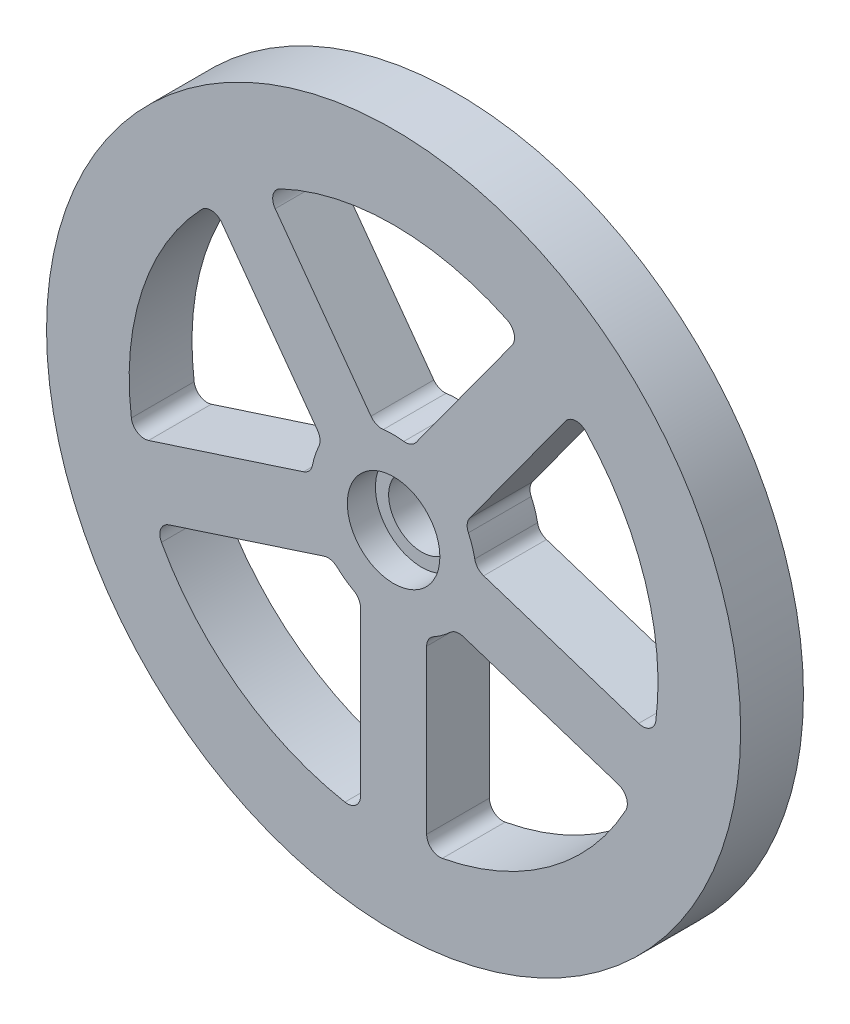
SolidWorks part; units mm, degrees
ref_plane "Plan de face" through (0, 0, 0) normal (0, 0, 1) x (1, 0, 0)
ref_plane "Plan de dessus" through (0, 0, 0) normal (0, 1, 0) x (1, 0, 0)
ref_plane "Plan de droite" through (0, 0, 0) normal (1, 0, 0) x (0, 0, -1)
sketch "Esquisse1" plane through (0, 0, 0) normal (0, 0, 1) x (1, 0, 0)
  circle A0 centre (0, 0) radius 105
  dimension "D1" = 210
extrude "Boss.-Extru.1" add sketch "Esquisse1" along normal blind 38
sketch "Esquisse2" plane through (0, 0, 38) normal (0, 0, 1) x (1, 0, 0)
  line L0 (0, 0) -> (0, 80) construction
  line L1 (5.3777, 24.4148) -> (38.5638, 70.0916)
  line L2 (-5.3777, 24.4148) -> (-38.5638, 70.0916)
  line L3 (24.8816, 2.4301) -> (78.5779, -15.0169)
  line L4 (21.558, 12.6591) -> (54.7442, 58.3359)
  line L5 (10, -22.9129) -> (10, -79.3725)
  line L6 (18.7013, -16.591) -> (72.3976, -34.038)
  line L7 (-18.7013, -16.591) -> (-72.3976, -34.038)
  line L8 (-10, -22.9129) -> (-10, -79.3725)
  line L9 (-21.558, 12.6591) -> (-54.7442, 58.3359)
  line L10 (-24.8816, 2.4301) -> (-78.5779, -15.0169)
  arc A0 (-38.5638, 70.0916) -> (38.5638, 70.0916) centre (0, 0) cw
  arc A1 (-5.3777, 24.4148) -> (5.3777, 24.4148) centre (0, 0) cw
  arc A2 (21.558, 12.6591) -> (24.8816, 2.4301) centre (0, 0) cw
  arc A3 (54.7442, 58.3359) -> (78.5779, -15.0169) centre (0, 0) cw
  arc A4 (18.7013, -16.591) -> (10, -22.9129) centre (0, 0) cw
  arc A5 (72.3976, -34.038) -> (10, -79.3725) centre (0, 0) cw
  arc A6 (-10, -22.9129) -> (-18.7013, -16.591) centre (0, 0) cw
  arc A7 (-10, -79.3725) -> (-72.3976, -34.038) centre (0, 0) cw
  arc A8 (-24.8816, 2.4301) -> (-21.558, 12.6591) centre (0, 0) cw
  arc A9 (-78.5779, -15.0169) -> (-54.7442, 58.3359) centre (0, 0) cw
  circle A10 centre (0, 0) radius 105 construction
  point P25 (0, 0)
  dimension "D1" = 25
  dimension "D2" = 25
  dimension "D4" = 20
  dimension "D3" = 5
extrude "Enlèv. mat.-Extru.1" cut sketch "Esquisse2" against normal through all both and the other way through all
sketch "Esquisse3" plane through (0, 0, 38) normal (0, 0, 1) x (1, 0, 0)
  circle A0 centre (0, 0) radius 10
  dimension "D1" = 20
extrude "Enlèv. mat.-Extru.2" cut sketch "Esquisse3" against normal through all both and the other way through all
sketch "Esquisse4" plane through (0, 0, 38) normal (0, 0, 1) x (1, 0, 0)
  circle A0 centre (0, 0) radius 14
  dimension "D1" = 28
extrude "Enlèv. mat.-Extru.3" cut sketch "Esquisse4" against normal blind 8.5
extrude "Enlèv. mat.-Extru.4" cut sketch "Esquisse4<2>" along normal blind 8.5 from surface starting at face at (10, 0, 0)
sketch "Esquisse4<2>" plane through (0, 0, 38) normal (0, 0, 1) x (1, 0, 0) same geometry as "Esquisse4"
fillet "Congé1" radius 4 20 edges at (-24.8816, 2.4301, 19) (-21.558, 12.6591, 19) (-5.3777, 24.4148, 19) (5.3777, 24.4148, 19) (21.558, 12.6591, 19) (24.8816, 2.4301, 19) (18.7013, -16.591, 19) (10, -22.9129, 19) (-10, -22.9129, 19) (-18.7013, -16.591, 19) (72.3976, -34.038, 19) (10, -79.3725, 19) (-72.3976, -34.038, 19) (-10, -79.3725, 19) (-78.5779, -15.0169, 19) (-54.7442, 58.3359, 19) (-38.5638, 70.0916, 19) (38.5638, 70.0916, 19) (54.7442, 58.3359, 19) (78.5779, -15.0169, 19)
fillet "Congé2" [suppressed] radius 10
fillet "Congé3" [suppressed] radius 3
sketch "Esquisse5" plane through (0, 0, 0) normal (0, 0, -1) x (-1, 0, 0)
  circle A0 centre (0, 0) radius 105
  dimension "D1" = 210
extrude "Enlèv. mat.-Extru.5" cut sketch "Esquisse5" against normal blind 19
